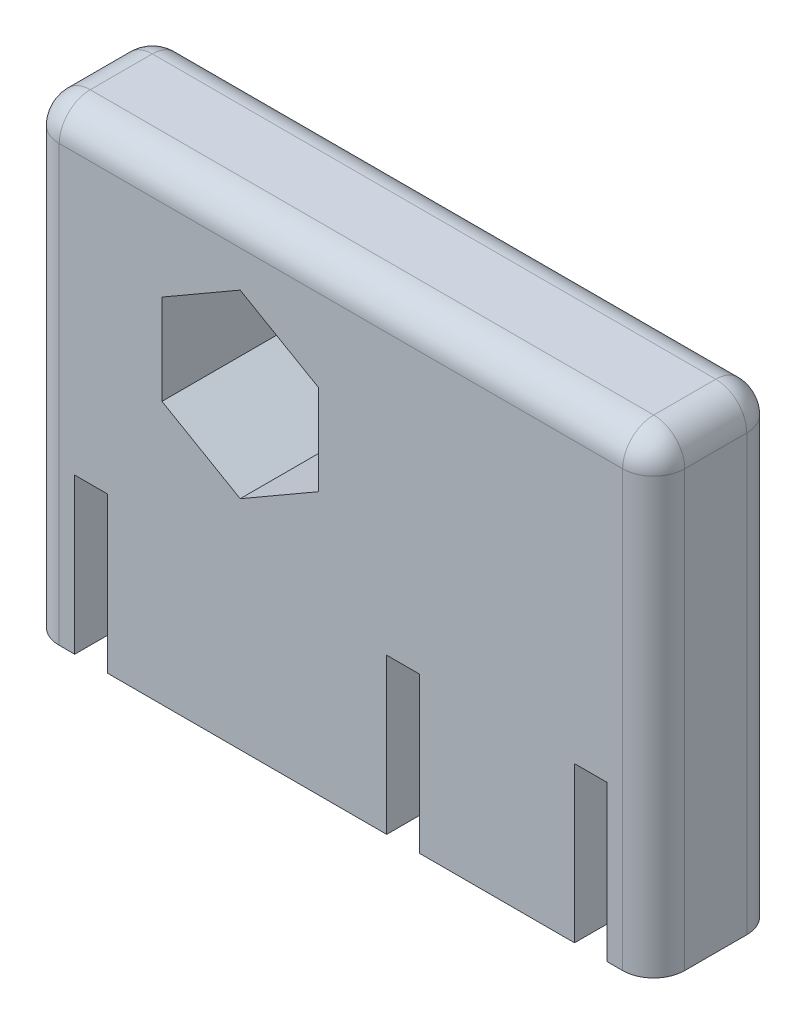
SolidWorks part; units mm, degrees
ref_plane "Front Plane" through (0, 0, 0) normal (0, 0, 1) x (1, 0, 0)
ref_plane "Top Plane" through (0, 0, 0) normal (0, 1, 0) x (1, 0, 0)
ref_plane "Right Plane" through (0, 0, 0) normal (1, 0, 0) x (0, 0, -1)
sketch "Sketch1" plane through (0, 0, 0) normal (0, 0, 1) x (1, 0, 0)
  line L0 (-17.15, -15) -> (-17.15, -5)
  line L1 (-20.15, -15) -> (-17.15, -15)
  line L2 (-20.15, -15) -> (-20.15, 15)
  line L3 (-20.15, 15) -> (20.15, 15)
  line L4 (20.15, -15) -> (20.15, 15)
  line L5 (-20.15, -15) -> (20.15, 15) construction
  line L6 (-20.15, 15) -> (20.15, -15) construction
  line L7 (-17.15, -5) -> (-15.05, -5)
  line L8 (-15.05, -5) -> (-15.05, -15)
  line L10 (2.95, -15) -> (2.95, -5)
  line L11 (2.95, -5) -> (5.05, -5)
  line L12 (5.05, -5) -> (5.05, -15)
  line L13 (15.05, -15) -> (15.05, -5)
  line L14 (15.05, -5) -> (17.15, -5)
  line L15 (17.15, -5) -> (17.15, -15)
  line L16 (-15.05, -15) -> (2.95, -15)
  line L17 (-1.4498, 7.741) -> (-6.4898, 10.6508)
  line L18 (-6.4898, 10.6508) -> (-11.5298, 7.741)
  line L19 (-11.5298, 7.741) -> (-11.5298, 1.9213)
  line L20 (-11.5298, 1.9213) -> (-6.4898, -0.9886)
  line L21 (-6.4898, -0.9886) -> (-1.4498, 1.9213)
  line L22 (-1.4498, 1.9213) -> (-1.4498, 7.741)
  line L23 (5.05, -15) -> (15.05, -15)
  line L24 (17.15, -15) -> (20.15, -15)
  circle A0 centre (-6.4898, 4.8311) radius 5.04 construction
  point P0 (0, 0)
  dimension "D1" = 40.3
  dimension "D2" = 30
  dimension "D3" = 2.1
  dimension "D4" = 2.1
  dimension "D5" = 2.1
  dimension "D6" = 10
  dimension "D7" = 10
  dimension "D8" = 10
  dimension "D9" = 3
  dimension "D10" = 18
  dimension "D11" = 10
  dimension "D12" = 5.04
  dimension "D13" = 0
extrude "Boss-Extrude1" add sketch "Sketch1" along normal blind 8
fillet "Fillet6" radius 2 1 edges at (-20.15, 15, 4)
fillet "Fillet7" radius 2 3 edges at (20.15, 0, 8) (20.15, 0, 0) (20.15, 15, 4)
fillet "Fillet8" radius 2 8 edges at (19.5642, 14.4142, 7.4142) (-19.5642, 14.4142, 8) (19.5642, 14.4142, 0.5858) (-20.15, -1, 0) (-19.5642, 14.4142, 0) (-20.15, -1, 8) (0, 15, 8) (0, 15, 0)
